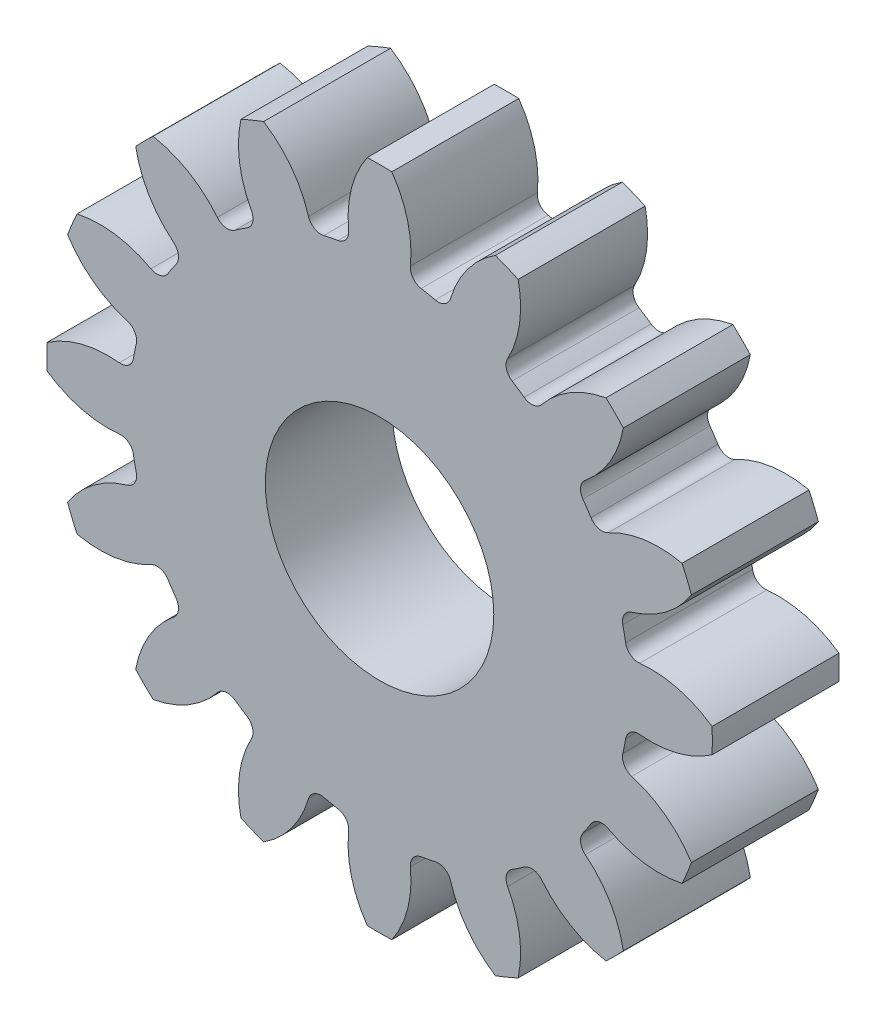
SolidWorks part; units mm, degrees
material "ABS"
ref_plane "Plane1" through (0, 0, 0) normal (0, 0, 1) x (1, 0, 0)
ref_plane "Plane2" through (0, 0, 0) normal (0, 1, 0) x (1, 0, 0)
ref_plane "Plane3" through (0, 0, 0) normal (1, 0, 0) x (0, 0, -1)
sketch "Esquisse1" plane through (0, 0, 0) normal (0, 0, 1) x (1, 0, 0)
  circle A0 centre (0, 0) radius 1.15
  dimension "D1" = 2.3
extrude "Base-Extrusion" add sketch "Esquisse1" along normal blind 2.5
sketch "Parametres" plane through (0, 0, 2.5) normal (0, 0, 1) x (1, 0, 0)
  line L0 (-33.4711, 41.7411) -> (-17.4711, 41.7411)
  line L1 (-33.4711, 34.0759) -> (-32.3061, 34.0759)
  line L2 (-33.4711, 23.0892) -> (-13.4711, 23.0892)
  line L3 (-33.4711, -2.6579) -> (-33.1221, -2.6579)
  line L4 (-38.9094, -12.5583) -> (-35.7678, -12.5583)
  line L5 (-48.8826, -19.2556) -> (-39.5626, -19.2556)
  line L6 (-48.8826, -29.9283) -> (-38.3976, -29.9283)
  line L7 (-48.8826, -38.2322) -> (-41.0188, -38.2322)
  line L8 (-48.8826, -45.1309) -> (-40.1246, -45.1309)
  line L9 (-48.8826, -60.7647) -> (-47.0526, -60.7647)
  line L10 (-48.8826, -76.1039) -> (-46.9019, -76.1039)
  line L11 (-48.8826, -88.0795) -> (-48.3004, -88.0795)
  line L12 (-50.5648, -98.8973) -> (-51.3404, -98.8973)
  line L13 (16.9123, -61.9871) -> (28.1623, -61.9871)
  line L14 (18.5152, -81.0212) -> (31.4731, -81.0212)
  line L15 (8.671, -96.0481) -> (4.433, -96.0481)
  line L16 (-33.4711, 13.8609) -> (-21.4711, 13.8609)
sketch "Esquisse3" plane through (0, 0, 0) normal (0, 0, 1) x (1, 0, 0)
  line L0 (0, 0) -> (0, 29.3764) construction
  line L1 (-1.5341, 7.7127) -> (0, 0)
  line L2 (0, 0) -> (1.5341, 7.7127)
  line L3 (0, 0) -> (0.9882, 8.702) construction
  line L4 (0, 0) -> (0.3877, 10.4778) construction
  line L5 (0, 0) -> (0.9135, 9.2751) construction
  arc A0 (0.3877, 10.4778) -> (0.908, 7.8112) centre (-2.3706, 8.5556) cw
  arc A1 (-0.3877, 10.4778) -> (-0.908, 7.8112) centre (2.3706, 8.5556) ccw
  arc A2 (1.5341, 7.7127) -> (0.908, 7.8112) centre (0, 0) ccw
  arc A3 (-1.5341, 7.7127) -> (-0.908, 7.8112) centre (0, 0) cw
  arc A4 (0.3877, 10.4778) -> (-0.3877, 10.4778) centre (0, 0) ccw
  dimension "D4" = 22.5
  dimension "D5" = 8.7579
  dimension "D6" = 9.32
  dimension "D1" = 10.485
  dimension "D2" = 6.479
  dimension "D3" = 5.625
  dimension "D7" = 2.119
  dimension "D8" = 7.8638
extrude "Boss.-Extru.1" add sketch "Esquisse3" along normal blind 4
fillet "Congé1" radius 0.4078 2 edges at (0.908, 7.8112, 2) (-0.908, 7.8112, 2)
ref_axis "Axe1" through (0, 0, 54) along (0, 0, -1)
pattern_circular "Répétition circulaire4" count 16 every 22.5 about axis through (0, 0, 54) along (0, 0, -1) of "Boss.-Extru.1", "Congé1"
sketch "Esquisse8" plane through (0, 0, 4) normal (0, 0, 1) x (1, 0, 0)
  circle A0 centre (0, 0) radius 3.6
  dimension "D1" = 7.2
extrude "Enlèv. mat.-Extru.1" cut sketch "Esquisse8" against normal through all
equation "\"PI@Parametres\" = 3.141592654"
equation "\"Alpha_rad@Parametres\" = \"Alpha@Parametres\"*\"PI@Parametres\"/180"
equation "\"R@Parametres\" = \"Z@Parametres\"*\"m@Parametres\"/2"
equation "\"RT@Parametres\" = \"R@Parametres\"+\"m@Parametres\""
equation "\"RP@Parametres\" = \"R@Parametres\"-1.25*\"m@Parametres\""
equation "\"Rb@Parametres\" = \"R@Parametres\"*cos(\"Alpha_rad@Parametres\")"
equation "\"E@Parametres\" = \"PI@Parametres\"*\"R@Parametres\"/\"Z@Parametres\""
equation "\"Eb@Parametres\" = \"Rb@Parametres\"*((\"PI@Parametres\"*\"m@Parametres\"/(2*\"R@Parametres\"))+2*(tan(\"Alpha_rad@Parametres\")-\"Alpha_rad@Parametres\"))"
equation "\"As@Parametres\" = atn(sqr(\"RT@Parametres\"*\"RT@Parametres\"-\"Rb@Parametres\"*\"Rb@Parametres\")/\"Rb@Parametres\")"
equation "\"Et@Parametres\" = \"RT@Parametres\"*((\"E@Parametres\"/\"R@Parametres\")+2*(tan(\"Alpha_rad@Parametres\")-\"Alpha_rad@Parametres\"-tan(\"As@Parametres\")+\"As@Parametres\"))"
equation "\"Ap@Parametres\" = (\"E@Parametres\"/\"R@Parametres\")*180/\"PI@Parametres\""
equation "\"Ab@Parametres\" = (\"Eb@Parametres\"/\"Rb@Parametres\")*180/\"PI@Parametres\""
equation "\"At@Parametres\" = (\"Et@Parametres\"/\"RT@Parametres\")*180/\"PI@Parametres\""
equation "\"D7@Esquisse3\" = \"At@Parametres\"/2"
equation "\"D3@Esquisse3\"=\"Ap@Parametres\"/2"
equation "\"D2@Esquisse3\"=\"Ab@Parametres\"/2"
equation "\"D5@Esquisse3\"=\"Rb@Parametres\""
equation "\"D6@Esquisse3\"=\"R@Parametres\""
equation "\"D1@Esquisse3\"=\"RT@Parametres\""
equation "\"D4@Esquisse3\" = \"Ap@Parametres\"*2"
equation "\"D1@Congé1\" = 0.35*\"m@Parametres\""
equation "\"D2@Répétition circulaire4\" = \"Ap@Parametres\"*2"
equation "\"D1@Répétition circulaire4\" = \"Z@Parametres\""
equation "\"D8@Esquisse3\" = \"RP@Parametres\""
